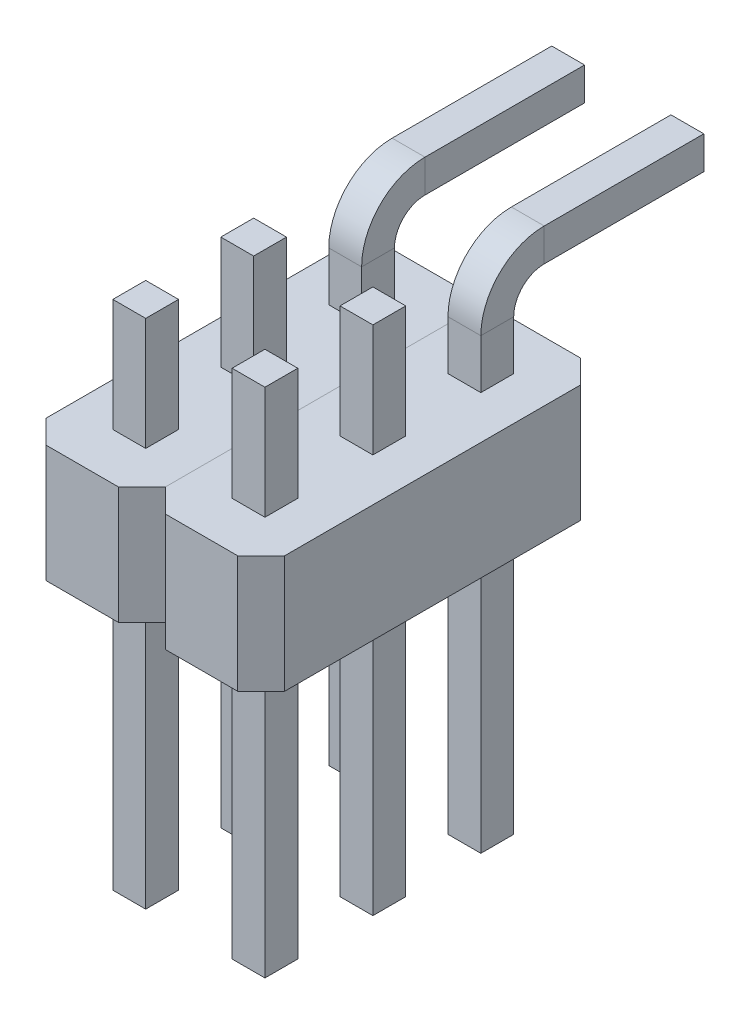
SolidWorks part; units mm, degrees
material "201 Annealed Stainless Steel (SS)"
ref_plane "Front Plane" through (0, 0, 0) normal (0, 0, 1) x (1, 0, 0)
ref_plane "Top Plane" through (0, 0, 0) normal (0, 1, 0) x (1, 0, 0)
ref_plane "Right Plane" through (0, 0, 0) normal (1, 0, 0) x (0, 0, -1)
sketch "Sketch1" plane through (0, 0, 0) normal (0, 1, 0) x (1, 0, 0)
  line L0 (0, 0) -> (2.54, 0)
  line L1 (0, 0) -> (0, -7.3)
  line L2 (0, -7.3) -> (2.54, -7.3)
  line L3 (2.54, 0) -> (2.54, -7.3)
  line L4 (0.92, -1) -> (1.62, -1)
  line L5 (0.92, -1) -> (0.92, -1.7)
  line L6 (0.92, -1.7) -> (1.62, -1.7)
  line L7 (1.62, -1) -> (1.62, -1.7)
  line L8 (0.92, -5.6) -> (1.62, -5.6)
  line L9 (0.92, -5.6) -> (0.92, -6.3)
  line L10 (0.92, -6.3) -> (1.62, -6.3)
  line L11 (1.62, -5.6) -> (1.62, -6.3)
  line L12 (0.92, -3.3) -> (1.62, -3.3)
  line L13 (0.92, -3.3) -> (0.92, -4)
  line L14 (0.92, -4) -> (1.62, -4)
  line L15 (1.62, -3.3) -> (1.62, -4)
  dimension "D1" = 7.3
  dimension "D2" = 2.54
  dimension "D3" = 0.92
  dimension "D4" = 1
  dimension "D5" = 0.7
  dimension "D6" = 1.6
  dimension "D7" = 1.6
ref_plane "Plane1" through (1.25, 0, 0) normal (1, 0, 0) x (0, 0, -1)
sketch "Sketch2" plane through (1.25, 0, 0) normal (1, 0, 0) x (0, 0, -1)
  line L0 (-5.95, 8.15) -> (-5.95, -6)
  line L1 (-3.65, 5.85) -> (-3.65, -6)
  line L2 (-1.35, 3.55) -> (-1.35, -6)
  line L3 (-4.95, 9.15) -> (3.05, 9.15)
  line L4 (0, 0) -> (-7.3, 0) construction
  line L5 (-2.65, 6.85) -> (3.05, 6.85)
  line L6 (-0.35, 4.55) -> (3.05, 4.55)
  arc A0 (-1.35, 3.55) -> (-0.35, 4.55) centre (-0.35, 3.55) cw
  arc A1 (-3.65, 5.85) -> (-2.65, 6.85) centre (-2.65, 5.85) cw
  arc A2 (-5.95, 8.15) -> (-4.95, 9.15) centre (-4.95, 8.15) cw
  point P19 (-5.95, 9.15)
  dimension "D9" = 1
  dimension "D1" = 15.15
  dimension "D2" = 2.3
  dimension "D3" = 2.3
  dimension "D4" = 1.35
  dimension "D5" = 6
  dimension "D6" = 9
  dimension "D7" = 2.3
  dimension "D8" = 2.3
sweep "Sweep3" add profiles "Sketch1" path "Sketch2"
sweep "Sweep4" add profiles "Sketch1<5>" path "Sketch2<6>"
sketch "Sketch1<5>" plane through (0, 0, 0) normal (0, 1, 0) x (1, 0, 0) same geometry as "Sketch1"
sketch "Sketch2<6>" plane through (1.25, 0, 0) normal (1, 0, 0) x (0, 0, -1) same geometry as "Sketch2"
sweep "Sweep5" add profiles "Sketch1<6>" path "Sketch2<7>"
sketch "Sketch1<6>" plane through (0, 0, 0) normal (0, 1, 0) x (1, 0, 0) same geometry as "Sketch1"
sketch "Sketch2<7>" plane through (1.25, 0, 0) normal (1, 0, 0) x (0, 0, -1) same geometry as "Sketch2"
extrude "Boss-Extrude1" add sketch "Sketch1<7>" along normal blind 2.5 contours L3 L0 L1 L2 L4 L7 L6 L5 L8 L11 L10 L9 L12 L15 L14 L13 region at (1.27, 0, 0.0773)
sketch "Sketch1<7>" plane through (0, 0, 0) normal (0, 1, 0) x (1, 0, 0) same geometry as "Sketch1"
chamfer "Chamfer1" distance 0.5 angle 45 4 edges at (0, 1.25, 0) (2.54, 1.25, 0) (0, 1.25, 7.3) (2.54, 1.25, 7.3)
pattern_linear "LPattern1" count 2 spacing 2.54 along (1, 0, 0) of bodies 104
sketch "Sketch3" plane through (0, 4.9, 0) normal (0, 1, 0) x (1, 0, 0)
  line L0 (0, 3.05) -> (5.08, 3.05)
  line L1 (5.08, 3.05) -> (5.08, -7.3)
  line L2 (5.08, -7.3) -> (0, -7.3)
  line L3 (0, -7.3) -> (0, 3.05)
  line L4 (1.62, 3.05) -> (0.92, 3.05) construction
  line L7 (0, -7.3) -> (2.54, -7.3) construction
  line L8 (5.08, -0.5) -> (5.08, -6.8) construction
  point P7 (0, 5.6362)
extrude "Cut-Extrude1" cut sketch "Sketch3" along normal through all contours L3 L0 L1 L2
